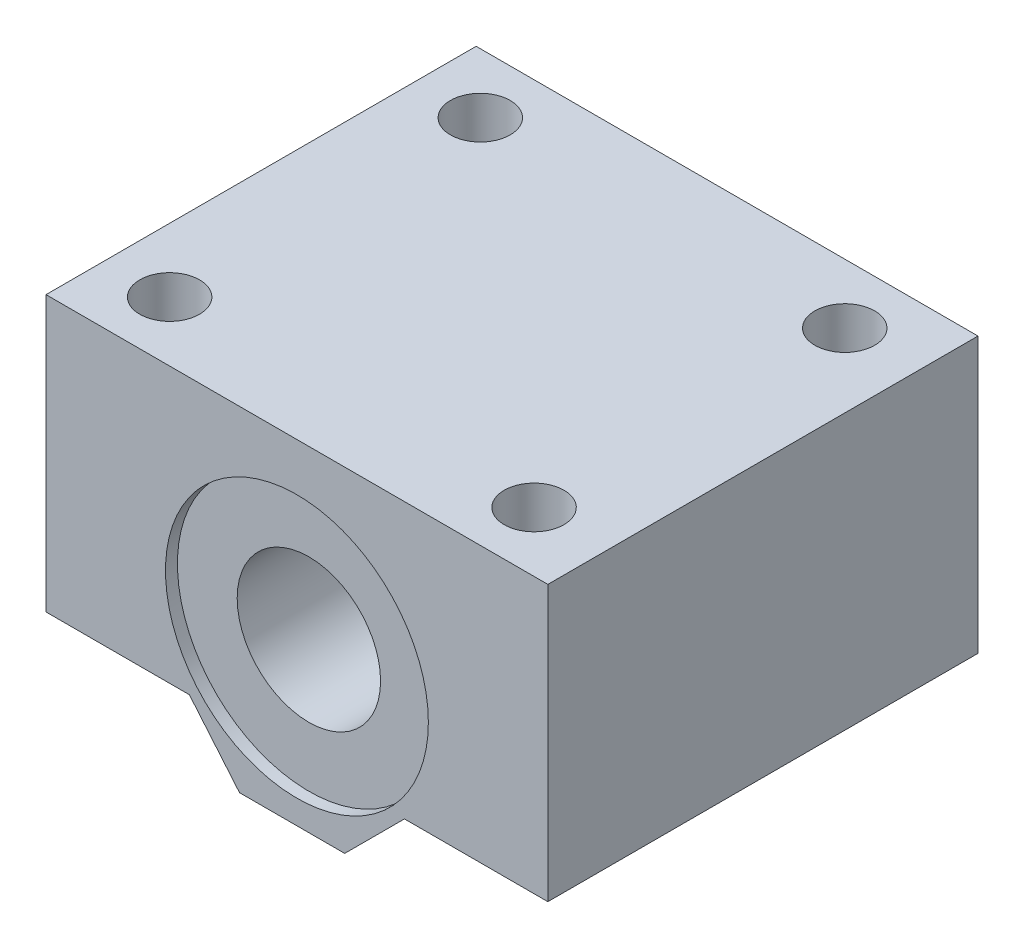
SolidWorks part; units mm, degrees
ref_plane "Front Plane" through (0, 0, 0) normal (0, 0, 1) x (1, 0, 0)
ref_plane "Top Plane" through (0, 0, 0) normal (0, 1, 0) x (1, 0, 0)
ref_plane "Right Plane" through (0, 0, 0) normal (1, 0, 0) x (0, 0, -1)
sketch "Sketch1" plane through (0, 0, 0) normal (0, 0, 1) x (1, 0, 0)
  line L1 (-21, -14) -> (21, -14)
  line L2 (-21, -14) -> (-21, 14)
  line L3 (-21, 14) -> (21, 14)
  line L4 (21, -14) -> (21, 14)
  line L5 (-21, -14) -> (21, 14) construction
  line L6 (-21, 14) -> (21, -14) construction
  circle A0 centre (0, -1) radius 6
  point P0 (0, 0)
  dimension "D3" = 12
  dimension "D1" = 42
  dimension "D2" = 28
  dimension "D4" = 21
  dimension "D5" = 15
extrude "Boss-Extrude1" add sketch "Sketch1" along normal mid plane 36
sketch "Sketch6" plane through (0, 0, 18) normal (0, 0, 1) x (1, 0, 0)
  line L1 (-21, 14) -> (-21, -14) construction
  line L7 (21, -14) -> (21, 14) construction
  line L11 (-21, -9) -> (-9, -9)
  line L12 (-9, -9) -> (-4.8045, -14)
  line L13 (-21, -14) -> (21, -14) construction
  line L14 (-4.8045, -14) -> (-21, -14)
  line L15 (-21, -14) -> (-21, -9)
  line L16 (21, -9) -> (9, -9)
  line L17 (9, -9) -> (4, -14)
  line L18 (4, -14) -> (21, -14)
  line L19 (21, -14) -> (21, -9)
  dimension "D6" = 12
  dimension "D7" = 135
  dimension "D8" = 5
  dimension "D9" = 130
  dimension "D10" = 12
extrude "Cut-Extrude5" cut sketch "Sketch6" against normal through all
sketch "Sketch2" plane through (0, 14, 0) normal (0, -1, 0) x (-1, 0, 0)
  line L0 (0.4023, -18) -> (0.4023, 18) construction
  line L1 (4.8045, -18) -> (-4, -18) construction
  line L2 (4.8045, 18) -> (-4, 18) construction
  line L3 (21, 0) -> (-21, 0) construction
  line L4 (21, -18) -> (21, 18) construction
  line L5 (-21, -18) -> (-21, 18) construction
  circle A0 centre (15.6523, -13) radius 2.15
  circle A1 centre (-14.8477, -13) radius 2.15
  circle A2 centre (-14.8477, 13) radius 2.15
  circle A3 centre (15.6523, 13) radius 2.15
  dimension "D1" = 4.3
  dimension "D2" = 4.3
  dimension "D3" = 4.3
  dimension "D4" = 4.3
  dimension "D5" = 15.25
  dimension "D6" = 15.25
  dimension "D7" = 15.25
  dimension "D8" = 15.25
  dimension "D9" = 13
  dimension "D10" = 13
  dimension "D11" = 13
  dimension "D12" = 13
extrude "Cut-Extrude1" cut sketch "Sketch2" along normal through all
sketch "Sketch3" plane through (0, 14, 0) normal (0, -1, 0) x (1, 0, 0)
  circle A0 centre (-15.6523, 13) radius 2.5
  circle A1 centre (14.8477, 13) radius 2.5
  circle A2 centre (14.8477, -13) radius 2.5
  circle A3 centre (-15.6523, -13) radius 2.5
  dimension "D1" = 5
  dimension "D2" = 5
  dimension "D3" = 5
  dimension "D4" = 5
extrude "Cut-Extrude2" cut sketch "Sketch3" along normal blind 12
sketch "Sketch4" plane through (0, 0, 18) normal (0, 0, 1) x (1, 0, 0)
  circle A0 centre (0, -1) radius 11
  dimension "D1" = 22
extrude "Cut-Extrude3" cut sketch "Sketch4" against normal blind 1
sketch "Sketch5" plane through (0, 0, -18) normal (0, 0, -1) x (-1, 0, 0)
  circle A0 centre (0, -1) radius 11
  dimension "D1" = 22
extrude "Cut-Extrude4" cut sketch "Sketch5" against normal blind 1
